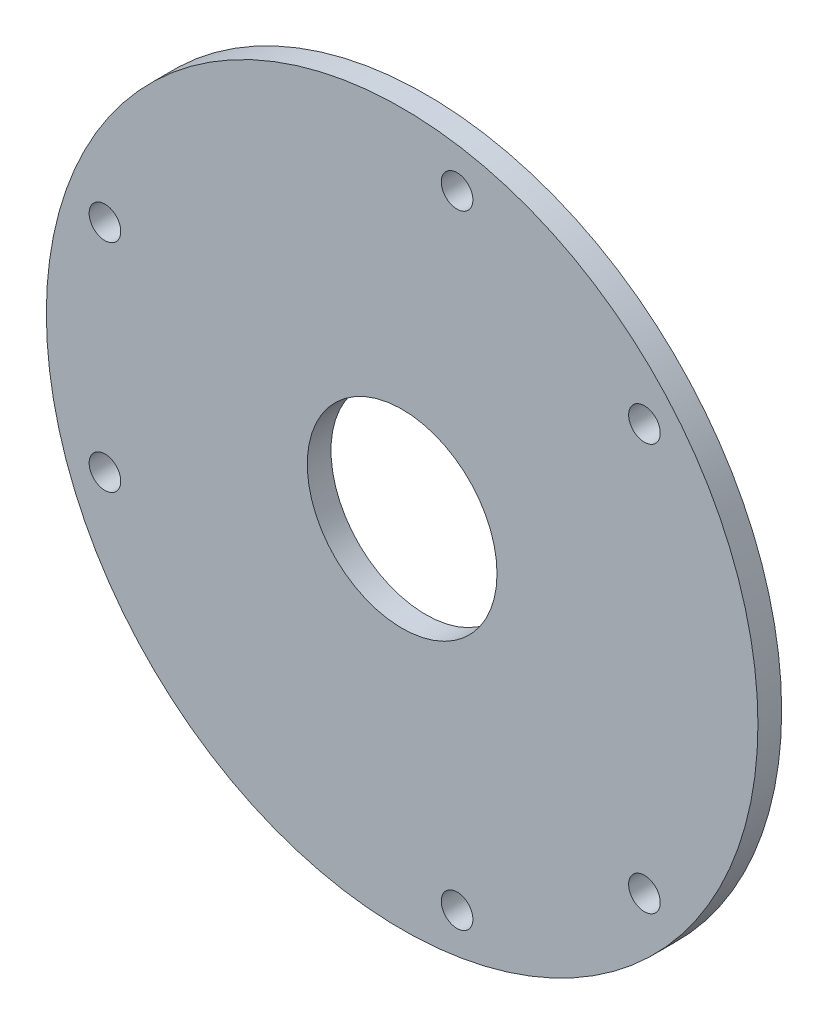
SolidWorks part; units mm, degrees
material "ABS PC"
ref_plane "Front Plane" through (0, 0, 0) normal (0, 0, 1) x (1, 0, 0)
ref_plane "Top Plane" through (0, 0, 0) normal (0, 1, 0) x (1, 0, 0)
ref_plane "Right Plane" through (0, 0, 0) normal (1, 0, 0) x (0, 0, -1)
sketch "Sketch1" plane through (0, 0, 0) normal (0, 0, 1) x (1, 0, 0)
  circle A0 centre (0, 0) radius 45
  circle A1 centre (-37.5877, 13.6808) radius 2
  circle A2 centre (6.9459, 39.3923) radius 2
  circle A3 centre (30.6418, 25.7115) radius 2
  circle A4 centre (-37.5877, -13.6808) radius 2
  circle A5 centre (6.9459, -39.3923) radius 2
  circle A6 centre (30.6418, -25.7115) radius 2
  circle A7 centre (0, 0) radius 12
extrude "Boss-Extrude1" add sketch "Sketch1" along normal blind 3
